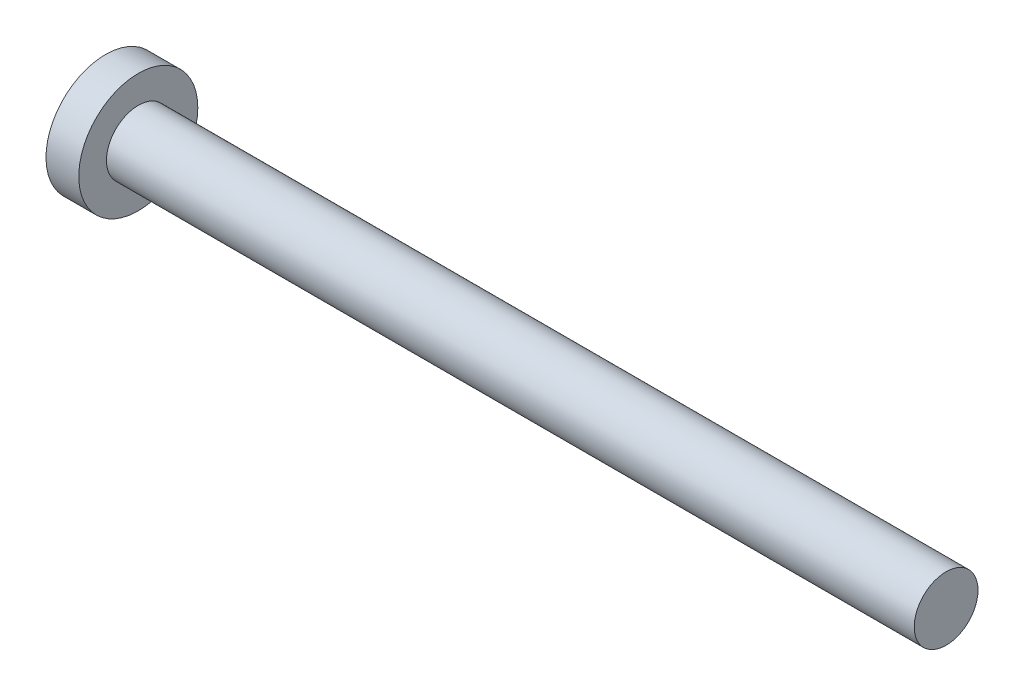
SolidWorks part; units mm, degrees
ref_plane "Front" through (0, 0, 0) normal (0, 0, 1) x (1, 0, 0)
ref_plane "Top" through (0, 0, 0) normal (0, 1, 0) x (1, 0, 0)
ref_plane "Right" through (0, 0, 0) normal (1, 0, 0) x (0, 0, -1)
sketch "Sketch1" plane through (0, 0, 0) normal (0, 0, 1) x (1, 0, 0)
  line L0 (40.4, 1.5) -> (3.4, 1.5)
  line L1 (2.4, 1.8) -> (2.4, 2.8)
  line L2 (2.4, 2.8) -> (0.8575, 2.8)
  line L3 (3.4, 1.5) -> (2.7, 1.5) construction
  line L4 (40.4, 1.5) -> (40.4, 0)
  line L5 (4.5158, 0) -> (-13.5157, 0) construction
  line L6 (40.4, 0) -> (0, 0)
  line L7 (3.4, 1.5) -> (2.4, 1.5)
  line L8 (2.4, 1.5) -> (2.4, 1.8)
  arc A0 (0.8575, 2.8) -> (0, 0) centre (5, 0) ccw
  arc A1 (2.4, 1.8) -> (2.7, 1.5) centre (2.7, 1.8) ccw construction
  dimension "k" = 2.4
revolve "Base" add sketch "Sketch1" angle 360 about L5
cosmetic thread "ThreadCosmetic1" [suppressed] parameters "bb"=38, "THD_MINOR"=2.459
sketch "Sketch6" plane through (0, 0, 0) normal (1, 0, 0) x (0, 0, -1)
  line L0 (-1.9271, 0) -> (2.0512, 0) construction
  line L1 (0, 1.8651) -> (0, -2.0207) construction
  line L2 (0.3, 0.3) -> (0.3, 1.5)
  line L3 (0.3, 1.5) -> (-0.3, 1.5)
  line L4 (-0.3, 0.3) -> (-0.3, 1.5)
  line L5 (0.3, 0.3) -> (1.5, 0.3)
  line L6 (1.5, 0.3) -> (1.5, -0.3)
  line L7 (-1.5, 0.3) -> (-1.5, -0.3)
  line L8 (-0.3, 0.3) -> (-1.5, 0.3)
  line L9 (-0.3, -0.3) -> (-1.5, -0.3)
  line L10 (0.3, -0.3) -> (1.5, -0.3)
  line L11 (-0.3, -0.3) -> (-0.3, -1.5)
  line L12 (0.3, -1.5) -> (-0.3, -1.5)
  line L13 (0.3, -0.3) -> (0.3, -1.5)
  point P16 (-1.5, 0)
  point P17 (1.5, 0)
extrude "CrossRecess" cut sketch "Sketch6" along normal blind 1.68
fillet "Fillet5" radius 0.3 4 edges at (0.849, -0.3, 0.3) (0.849, -0.3, -0.3) (0.849, 0.3, 0.3) (0.849, 0.3, -0.3)
draft "Draft1" type of draft neutral plane draft angle 30 neutral plane "Right" faces to draft 4 face at (0.9575, -1.5, 0) face at (0.9575, 0, -1.5) face at (0.9575, 0, 1.5) face at (0.9575, 1.5, 0) neutral plane through (0, 0, 0) neutral plane normal (1, 0, 0) reverse direction yes parameters "D1"=30
sketch "Sketch7" plane through (0, 0, 0) normal (1, 0, 0) x (0, 0, -1)
  line L0 (-2.0126, 0) -> (1.9757, 0) construction
  line L1 (0, 1.9314) -> (0, -2.0126) construction
  line L2 (0, 0) -> (1.5555, 1.5555) construction
  line L3 (0, 0.4483) -> (1.0607, 1.0607)
  line L4 (-1.5402, 1.5402) -> (0, 0) construction
  line L5 (0.4483, 0) -> (1.0607, 1.0607)
  line L6 (0, -0.4483) -> (1.0607, -1.0607)
  line L7 (0.4483, 0) -> (1.0607, -1.0607)
  line L8 (-0.4483, 0) -> (-1.0607, -1.0607)
  line L9 (0, -0.4483) -> (-1.0607, -1.0607)
  line L10 (-0.4483, 0) -> (-1.0607, 1.0607)
  line L11 (0, 0.4483) -> (-1.0607, 1.0607)
  dimension "D3" = 15
extrude "Cut-Extrude3" [suppressed] cut sketch "Sketch7" along normal blind 40.2 draft 9
sketch "Sketch8" plane through (0, 0, 0) normal (0, 0, 1) x (1, 0, 0)
  line L0 (15.4, 1.5) -> (14.15, 1.2295)
  line L1 (14.15, 1.2295) -> (2.4, 1.2295)
  line L2 (40.4, -1.5) -> (40.4, 1.5) construction
  line L3 (2.4, -2.8) -> (2.4, 2.8) construction
  line L6 (2.4, 1.2295) -> (2.4, 2.8)
  line L7 (2.4, 2.8) -> (15.4, 2.8)
  line L8 (15.4, 2.8) -> (15.4, 1.5)
  line L9 (73.4853, 0) -> (63.9694, 0) construction
  dimension "x" = 1.25
sketch "Sketch9" plane through (0, 0, 0) normal (0, 0, 1) x (1, 0, 0)
  line L0 (40.4, 1.2657) -> (40.5353, 1.5)
  line L1 (40.5353, 1.5) -> (40.5353, 1.7705)
  line L2 (40.5353, 1.7705) -> (40.2647, 1.7705)
  line L3 (40.2647, 1.7705) -> (40.2647, 1.5)
  line L4 (40.2647, 1.5) -> (40.4, 1.2657)
  line L5 (40.4, -1.5) -> (40.4, 1.5) construction
  line L6 (0, 0) -> (76.7811, 0) construction
  dimension "D1" = 3
  dimension "D2" = 0.2705
revolve "Cut-Revolve10" [suppressed] cut sketch "Sketch9" angle 360 about L6
pattern_linear "LPattern10" [suppressed] count 117 spacing 0.3246 along (-1, 0, 0) of bodies 105
equation "\"D1@Sketch6\" = \"m@Sketch6\" / 5"
equation "\"D1@CrossRecess\" = 0.7*\"k@Sketch1\""
equation "\"D1@Sketch9\" = \"d@Sketch1\" "
equation "\"D2@Sketch9\" =  ( \"d@Sketch1\" - \"THD_MINOR@ThreadCosmetic1\" )  / 2"
equation "\"D3@LPattern10\" =\"D2@Sketch9\" * 1.2"
equation "\"D1@LPattern10\" = \"bb@ThreadCosmetic1\" / \"D3@LPattern10\" "
